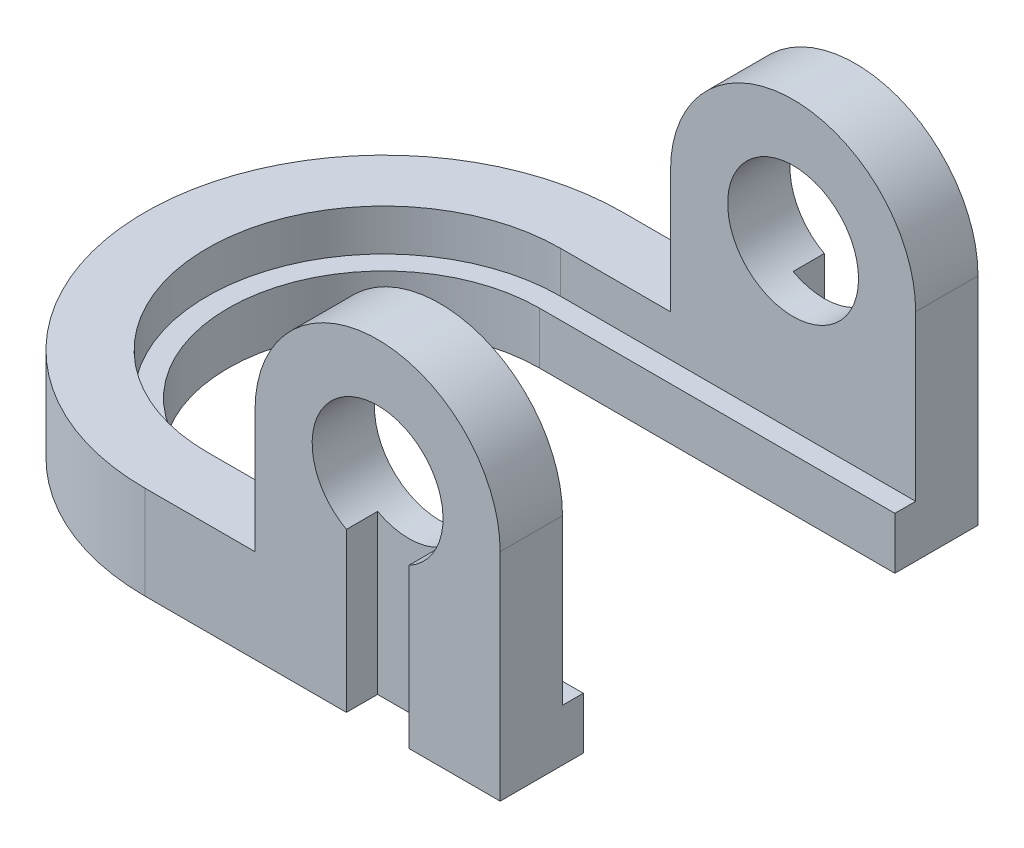
SolidWorks part; units mm, degrees
ref_plane "前视基准面" through (0, 0, 0) normal (0, 0, 1) x (1, 0, 0)
ref_plane "上视基准面" through (0, 0, 0) normal (0, 1, 0) x (1, 0, 0)
ref_plane "右视基准面" through (0, 0, 0) normal (1, 0, 0) x (0, 0, -1)
other "Configuration Table"
sketch "草图1" plane through (0, 0, 0) normal (0, 1, 0) x (1, 0, 0)
  line L0 (0, 85) -> (171, 85)
  line L1 (0, 115) -> (171, 115)
  line L3 (0, -115) -> (171, -115)
  line L4 (171, 115) -> (171, 75)
  line L5 (0, -85) -> (171, -85)
  line L6 (0, 75) -> (171, 75)
  line L7 (0, -75) -> (171, -75)
  line L9 (171, -75) -> (171, -115)
  arc A0 (0, 85) -> (0, -85) centre (0, 0) ccw
  arc A2 (0, 75) -> (0, -75) centre (0, 0) ccw
  arc A3 (0, 115) -> (0, -115) centre (0, 0) ccw
  point P1 (0, 0)
  dimension "D1" = 75
  dimension "D2" = 115
  dimension "D5" = 10
  dimension "D3" = 171
  dimension "D4" = 230
extrude "凸台-拉伸2" add sketch "草图1" along normal blind 25 contours L1 A3 L3 L9 L5 A0 L0 L4 | A2 L6 L4 L0 A0 L5 L9 L7 region at (-88.6701, 0, 0) region at (85.5, 0, -81.927)
extrude "凸台-拉伸3" add sketch "草图1<5>" along normal blind 45 contours L1 A3 L3 L9 L5 A0 L0 L4 region at (-88.6701, 0, 0)
sketch "草图1<5>" plane through (0, 0, 0) normal (0, 1, 0) x (1, 0, 0) same geometry as "草图1"
sketch "草图2" plane through (0, 0, -85) normal (0, 0, 1) x (1, 0, 0)
  line L0 (0, 0) -> (171, 0) construction
  line L1 (171, 25) -> (53, 25)
  line L2 (171, 25) -> (171, 104)
  line L4 (53, 25) -> (53, 104)
  arc A0 (171, 104) -> (53, 104) centre (112, 104) ccw
  circle A1 centre (112, 104) radius 31.5
  dimension "D1" = 118
  dimension "D2" = 63
  dimension "D3" = 104
  dimension "D4" = 118
extrude "凸台-拉伸4" add sketch "草图2" against normal blind 30
sketch "草图3" plane through (0, 0, -115) normal (0, 0, -1) x (-1, 0, 0)
  line L0 (0, 0) -> (-171, 0) construction
  line L1 (-97, -86.4239) -> (-127, -86.4239)
  line L2 (-97, -86.4239) -> (-97, 86.4239)
  line L3 (-97, 86.4239) -> (-127, 86.4239)
  line L4 (-127, -86.4239) -> (-127, 86.4239)
  line L5 (-97, -86.4239) -> (-127, 86.4239) construction
  line L6 (-97, 86.4239) -> (-127, -86.4239) construction
  point P0 (-112, 0)
  point P7 (0, 0)
  dimension "D1" = 30
  dimension "D2" = 172.8478
  dimension "D3" = 112
extrude "切除-拉伸1" cut sketch "草图3" against normal blind 15
mirror "镜向4" about plane through (0, 0, 0) normal (0, 0, 1) of "切除-拉伸1", "凸台-拉伸4"
